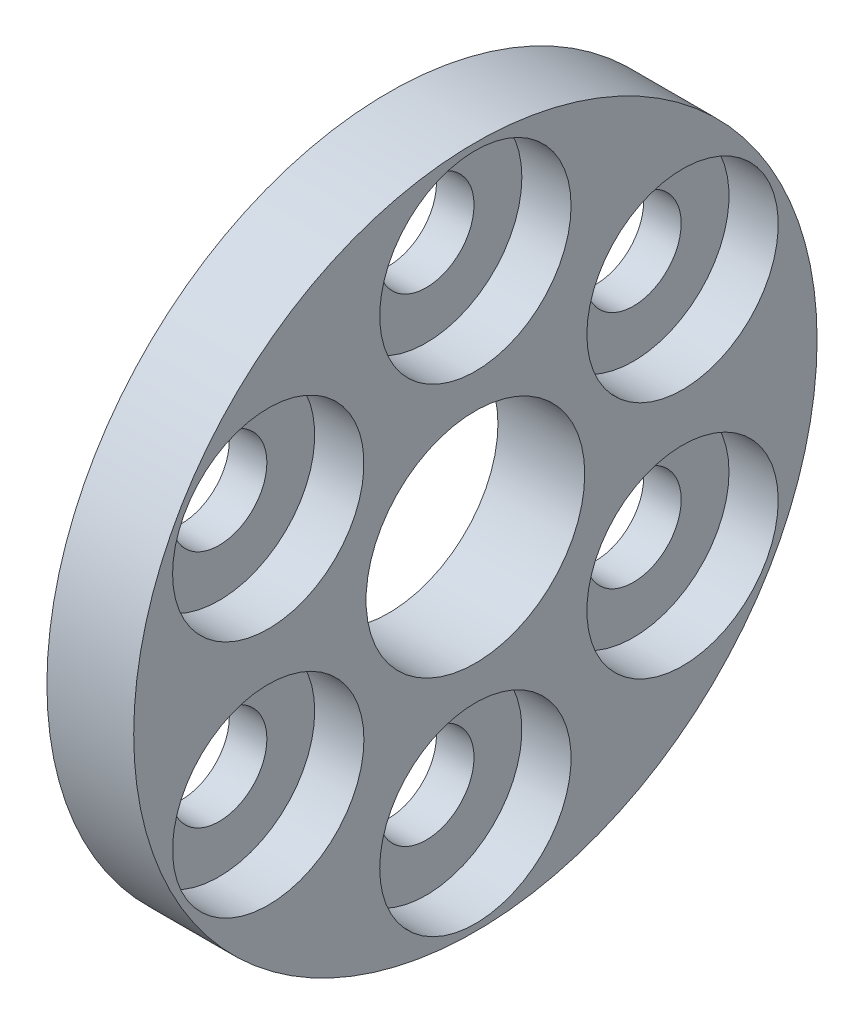
SolidWorks part; units mm, degrees
material "1023 Carbon Steel Sheet (SS)"
ref_plane "Front Plane" through (0, 0, 0) normal (0, 0, 1) x (1, 0, 0)
ref_plane "Top Plane" through (0, 0, 0) normal (0, 1, 0) x (1, 0, 0)
ref_plane "Right Plane" through (0, 0, 0) normal (1, 0, 0) x (0, 0, -1)
sketch "Sketch1" plane through (0, 0, 0) normal (1, 0, 0) x (0, 0, -1)
  circle A0 centre (0, 0) radius 12.5
  dimension "D1" = 25
extrude "Boss-Extrude1" add sketch "Sketch1" along normal blind 3.175
sketch "Sketch2" plane through (3.175, 0, 0) normal (1, 0, 0) x (0, 0, -1)
  circle A0 centre (0, 8.75) radius 1.75
  dimension "D1" = 3.5
  dimension "D2" = 8.75
sketch "Sketch3" plane through (3.175, 0, 0) normal (1, 0, 0) x (0, 0, -1)
  circle A0 centre (0, 0) radius 4
  dimension "D1" = 8
extrude "Cut-Extrude1" cut sketch "Sketch3" against normal through all
extrude "Cut-Extrude2" cut sketch "Sketch2" against normal through all
sketch "Sketch4" plane through (3.175, 0, 0) normal (1, 0, 0) x (0, 0, -1)
  line L1 (1.5877, 11.5) -> (-1.5877, 11.5)
  line L2 (-1.5877, 11.5) -> (-3.1754, 8.75)
  line L3 (-3.1754, 8.75) -> (-1.5877, 6)
  line L4 (-1.5877, 6) -> (1.5877, 6)
  line L5 (1.5877, 6) -> (3.1754, 8.75)
  line L6 (3.1754, 8.75) -> (1.5877, 11.5)
  circle A0 centre (0, 8.75) radius 2.75 construction
  circle A1 centre (0, 8.75) radius 3.5
  circle M13 centre (0, 8.75) radius 1.75
  dimension "D2" = 7
  dimension "D1" = 5.5
extrude "Cut-Extrude3" cut sketch "Sketch4" against normal blind 1.8 contours L5 L6 L1 L2 L3 L4 M13 | A1 L6 L5 L4 L3 L2 L1 | M13 | L1 L2 L3 L4 L5 L6 | A1 region at (3.175, 10.083, -2.3088) region at (3.175, 8.75, 3.401) region at (3.175, 8.75, 0)
pattern_circular "CirPattern1" count 6 over 360 about axis through (3.175, 0, 0) along (1, 0, 0) of "Cut-Extrude3", "Cut-Extrude2"
